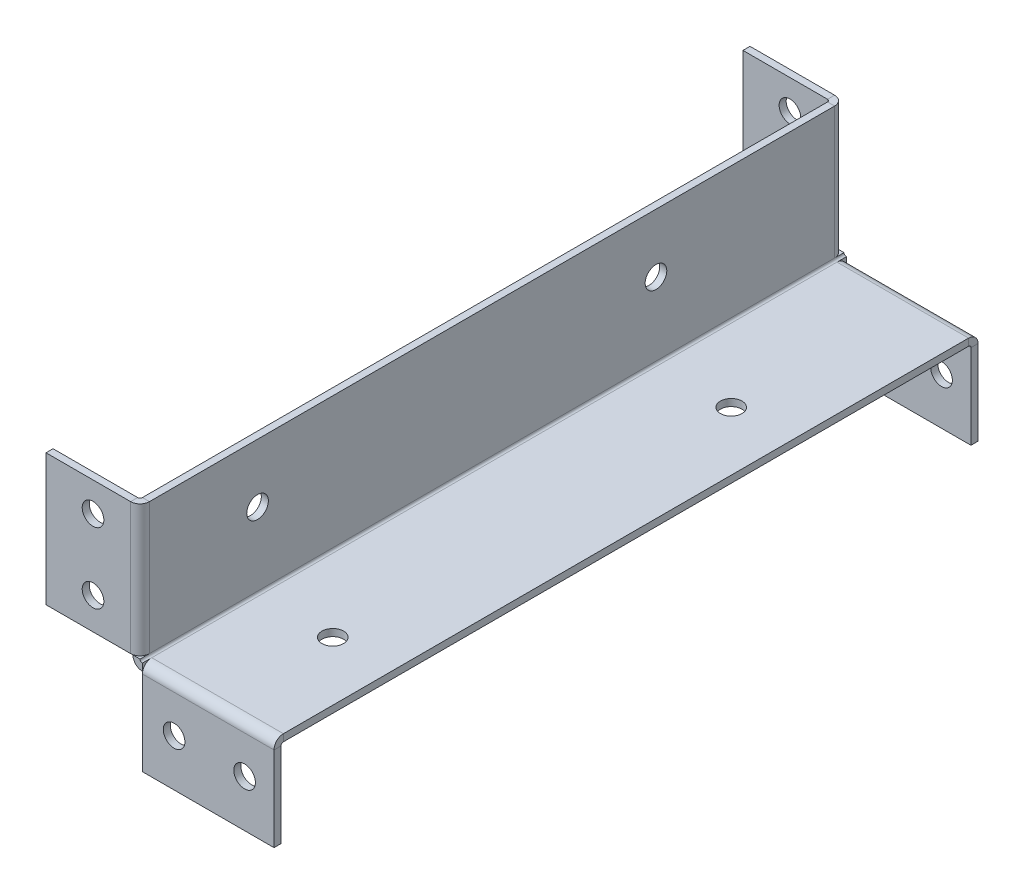
SolidWorks part; units mm, degrees
note: The reader was unsure of these and kept them because the rebuilt part matched: flange length of "Edge-Flange1", "Edge-Flange2".
ref_plane "Front Plane" through (0, 0, 0) normal (0, 0, 1) x (1, 0, 0)
ref_plane "Top Plane" through (0, 0, 0) normal (0, 1, 0) x (1, 0, 0)
ref_plane "Right Plane" through (0, 0, 0) normal (1, 0, 0) x (0, 0, -1)
sketch "Sketch1" plane through (0, 0, 0) normal (0, 1, 0) x (1, 0, 0)
  line L1 (30, 149.75) -> (-30, 149.75)
  line L2 (30, 149.75) -> (30, -149.75)
  line L3 (30, -149.75) -> (-30, -149.75)
  line L4 (-30, 149.75) -> (-30, -149.75)
  line L5 (30, 149.75) -> (-30, -149.75) construction
  line L6 (30, -149.75) -> (-30, 149.75) construction
  point P0 (0, 0)
  dimension "D1" = 60
  dimension "D2" = 299.5
sheet metal parameters "Sheet-Metal1" thickness 3 parameters "D1"=1
base flange "Base-Flange1" sketch "Sketch1" thickness 3 reverse thickness direction yes parameters "D1"=1
edge flange "Edge-Flange1" sketch "Sketch5" flange angle 90 flange length 60 flange position material inside bend radius 1 thickness 3 parameters "D6"=10
sketch "Sketch5" plane through (-30, 3, 0) normal (-1, 0, 0) x (0, 0, 1)
  line L2 (-149.75, 0) -> (-149.75, 57)
  line L3 (-149.75, 57) -> (149.75, 57)
  line L4 (149.75, 57) -> (149.75, 0)
  line L5 (-149.75, 0) -> (149.75, 0) construction
  line L6 (-149.75, 0) -> (149.75, 0)
bend "EdgeBend1" bend radius 1 bend angle 90 parameters "D5"=1
edge flange "Edge-Flange2" sketch "Sketch14" flange profiles "Sketch14", "Sketch15", "Sketch16", "Sketch17" flange angle 90 flange length 40 flange position material inside bend radius 1 thickness 3 relief none parameters "D6"=10, "D8"=0.5
sketch "Sketch14" plane through (-30, 0, 149.75) normal (0, 0, -1) x (0, -1, 0)
  line L1 (-4, 0) -> (-60, 0) construction
  line L2 (-60, 0) -> (-60, 37)
  line L3 (-60, 37) -> (-4, 37)
  line L4 (-4, 37) -> (-4, 0)
  line L5 (-4, 0) -> (-60, 0)
sketch "Sketch15" plane through (0, 0, 149.75) normal (0, 0, -1) x (1, 0, 0)
  line L0 (30, 0) -> (-26, 0) construction
  line L1 (30, 0) -> (-26, 0)
  line L2 (30, 0) -> (30, 37)
  line L3 (30, 37) -> (-26, 37)
  line L4 (-26, 37) -> (-26, 0)
sketch "Sketch16" plane through (-30, 0, -149.75) normal (0, 0, 1) x (0, 1, 0)
  line L0 (60, 0) -> (4, 0) construction
  line L1 (60, 0) -> (4, 0)
  line L2 (60, 0) -> (60, 37)
  line L3 (60, 37) -> (4, 37)
  line L4 (4, 37) -> (4, 0)
sketch "Sketch17" plane through (0, 0, -149.75) normal (0, 0, 1) x (-1, 0, 0)
  line L0 (26, 0) -> (-30, 0) construction
  line L1 (26, 0) -> (-30, 0)
  line L2 (26, 0) -> (26, 37)
  line L3 (26, 37) -> (-30, 37)
  line L4 (-30, 37) -> (-30, 0)
bend "EdgeBend2" bend radius 1 bend angle 90 parameters "D5"=2
bend "EdgeBend3" bend radius 1 bend angle 90 parameters "D5"=3
bend "EdgeBend4" bend radius 1 bend angle 90 parameters "D5"=4
bend "EdgeBend5" bend radius 1 bend angle 90 parameters "D5"=5
sketch "Sketch18" plane through (0, 0, 149.75) normal (0, 0, 1) x (1, 0, 0)
  line L0 (-26, 3) -> (30, 3) construction
  line L1 (-27, 60) -> (-27, 4) construction
  line L2 (-67, 60) -> (-31, 60) construction
  line L3 (30, -1) -> (30, -37) construction
  circle A0 centre (-47, 47.5) radius 4.6
  circle A1 centre (-47, 17.5) radius 4.6
  circle A2 centre (-12.5, -17) radius 4.6
  circle A3 centre (17.5, -17) radius 4.6
  dimension "D7" = 9.2
  dimension "D1" = 30
  dimension "D2" = 30
  dimension "D3" = 20
  dimension "D4" = 20
  dimension "D5" = 12.5
  dimension "D6" = 12.5
extrude "Extrude1" cut sketch "Sketch18" against normal through all normal cut yes
sketch "Sketch19" plane through (-27, 0, 0) normal (1, 0, 0) x (0, 0, -1)
  line L0 (-145.75, 60) -> (145.75, 60) construction
  line L1 (-149.75, 4) -> (-149.75, 60) construction
  line L2 (149.75, 4) -> (149.75, 60) construction
  circle A0 centre (-99.75, 35) radius 4.6
  circle A1 centre (69.75, 35) radius 4.6
  dimension "D4" = 9.2
  dimension "D2" = 80
  dimension "D3" = 50
  dimension "D1" = 25
extrude "Extrude2" cut sketch "Sketch19" against normal blind 3 normal cut yes
sketch "Sketch20" plane through (0, 3, 0) normal (0, 1, 0) x (1, 0, 0)
  line L0 (30, -145.75) -> (30, 145.75) construction
  line L1 (-26, -149.75) -> (30, -149.75) construction
  line L2 (30, 149.75) -> (-26, 149.75) construction
  circle A0 centre (5, 69.75) radius 4.6
  circle A1 centre (5, -99.75) radius 4.6
  dimension "D2" = 9.2
  dimension "D4" = 80
  dimension "D3" = 50
  dimension "D1" = 25
extrude "Extrude3" cut sketch "Sketch20" against normal blind 3 normal cut yes
flat pattern "Flat-Pattern1" [suppressed]
sketch "Bend-Lines1" plane through (0, 4, 0) normal (0, 1, 0) x (-1, 0, 0)
  line L0 (25, -126.4012) -> (-30, -126.4012) construction
  line L1 (82.8023, -126.4012) -> (27.8023, -126.4012) construction
  line L2 (-30, 126.4012) -> (25, 126.4012) construction
  line L3 (27.8023, 126.4012) -> (82.8023, 126.4012) construction
  line L4 (26.4012, -130) -> (26.4012, 130) construction
  line L5 (25, -126.4012) -> (-30, -126.4012) construction
  line L6 (82.8023, -126.4012) -> (27.8023, -126.4012) construction
  line L7 (-30, 126.4012) -> (25, 126.4012) construction
  line L8 (27.8023, 126.4012) -> (82.8023, 126.4012) construction
  line L9 (26.4012, -130) -> (26.4012, 130) construction
bend of the flat pattern "Flatten-<EdgeBend1>1"
bend of the flat pattern "Flatten-<EdgeBend2>1"
bend of the flat pattern "Flatten-<EdgeBend3>1"
bend of the flat pattern "Flatten-<EdgeBend4>1"
bend of the flat pattern "Flatten-<EdgeBend5>1"
